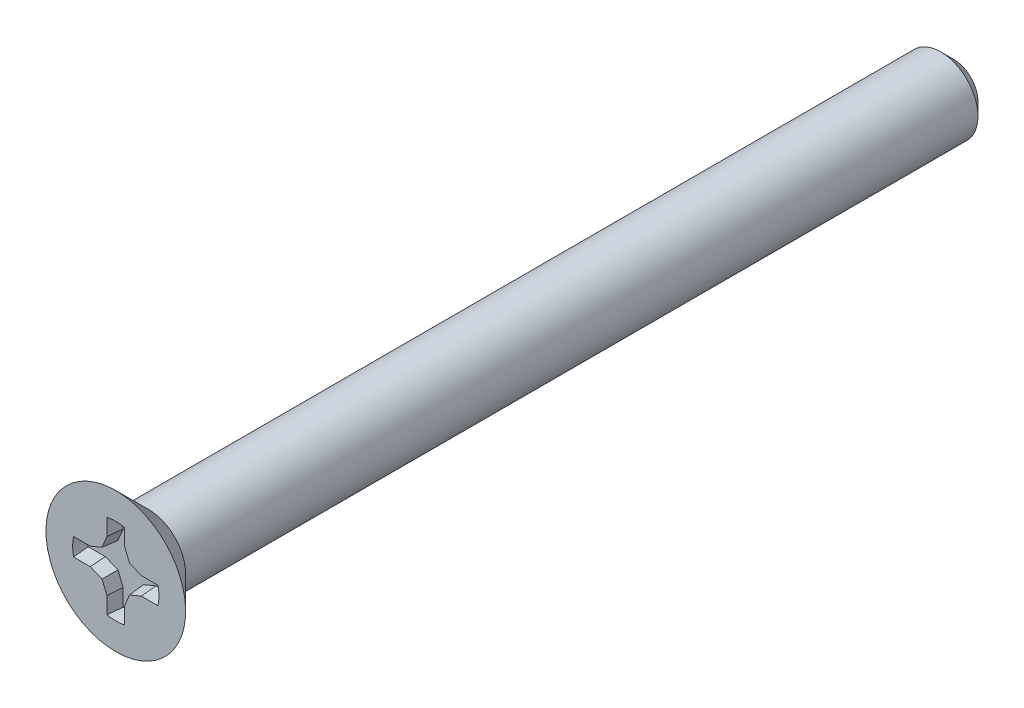
SolidWorks part; units mm, degrees
ref_plane "Front Plane" through (0, 0, 0) normal (0, 0, 1) x (1, 0, 0)
ref_plane "Top Plane" through (0, 0, 0) normal (0, 1, 0) x (1, 0, 0)
ref_plane "Right Plane" through (0, 0, 0) normal (1, 0, 0) x (0, 0, -1)
sketch "Sketch1" plane through (0, 0, 0) normal (1, 0, 0) x (0, 0, -1)
  line L0 (0, 0) -> (-0.96, 0) construction
  line L1 (-0.96, 1.5) -> (-0.96, -1.5) construction
  line L2 (-0.96, 1.5) -> (0, 0.54) construction
  line L3 (-0.96, -1.5) -> (0, -0.54) construction
  line L4 (0, 0.8) -> (0, -0.8) construction
  line L5 (0, 0) -> (17.04, 0) construction
  line L6 (0, 0.8) -> (0.35, 0.8) construction
  line L7 (0, 0.8) -> (-0.26, 0.8) construction
  line L8 (17.04, 0.54) -> (17.04, -0.54) construction
  point P6 (-0.96, 0)
  point P11 (0, 0)
  point P16 (-0.26, 0.8)
  point P17 (15.815, -0.8)
  point P20 (17.04, 0)
  point P21 (-0.48, 0)
  point P22 (15.815, -0.54)
  point P23 (17.04, -0.54)
  point P25 (17.04, 0.54)
  dimension "Head Height" = 0.96
  dimension "Head Diameter" = 3
  dimension "Countersink Angle" = 90
  dimension "Thread OD" = 1.6
  dimension "Length" = 18
  dimension "Thread Pitch" = 0.35
  dimension "D1" = 1.225
sketch "Sketch2" plane through (0, 0, 0) normal (0, 0, 1) x (1, 0, 0)
  line L0 (0.1905, 0.9271) -> (-0.1905, 0.9271) construction
  circle A0 centre (0, 0) radius 0.9271 construction
  point P3 (0, 0.9271)
  point P7 (0, 0.9271)
  dimension "Drive Dia" = 1.8542
  dimension "Drive Width" = 0.381
sketch "Sketch3" plane through (0, 0, 0) normal (1, 0, 0) x (0, 0, -1)
  line L0 (-0.96, 0) -> (-0.96, 1.5)
  line L1 (-0.96, 1.5) -> (-0.26, 0.8)
  line L2 (-0.96, 1.5) -> (0, 0.54) construction
  line L3 (0, 0.8) -> (0.35, 0.8) construction
  line L4 (-0.96, 0) -> (-0.26, 0)
  line L5 (0, 0) -> (-0.96, 0) construction
  line L6 (-0.26, 0) -> (-0.26, 0.8)
revolve "Revolve1" add sketch "Sketch3" angle 360 about L4
sketch "Sketch5" plane through (0, 0, 0) normal (1, 0, 0) x (0, 0, -1)
  line L0 (17.04, 0) -> (-0.26, 0)
  line L1 (0, 0) -> (17.04, 0) construction
  line L2 (-0.26, 0) -> (-0.26, 0.8)
  line L3 (-0.26, 0.8) -> (16.7635, 0.8)
  line L4 (16.7635, 0.8) -> (17.04, 0.5235)
  line L5 (17.04, 0.5235) -> (17.04, 0)
  line L6 (16.7635, 0.8) -> (17.04, 0.8) construction
  line L7 (17.04, 0.8) -> (17.04, 0.5235) construction
  line L8 (0, 0.8) -> (0.35, 0.8) construction
  line L9 (-0.26, -0.8) -> (-0.26, 0.8) construction
  dimension "D1" = 0.2765
revolve "Revolve2" add sketch "Sketch5" angle 360 about L0
sketch "Sketch4" plane through (0, 0, 0.96) normal (0, 0, 1) x (1, 0, 0)
  line L0 (0, 0) -> (0, 0.9271)
  line L1 (0, 0) -> (0.9271, 0)
  line L2 (0, 0) -> (0.5489, 0.5489) construction
  line L3 (0.1905, 0.9073) -> (0.1905, 0.5489)
  line L4 (0.1905, 0.5489) -> (0.1905, 0.1905) construction
  line L5 (0.5489, 0.1905) -> (0.1905, 0.1905) construction
  line L6 (0.9073, 0.1905) -> (0.5489, 0.1905)
  line L7 (0.1905, 0.5489) -> (0.2955, 0.2955)
  line L8 (0.2955, 0.2955) -> (0.5489, 0.1905)
  line L9 (0, 0.9271) -> (0, 1.5) construction
  line L10 (0, 1.5) -> (0, -1.5) construction
  circle A0 centre (0, 0) radius 0.9271 construction
  arc A1 (0, 0.9271) -> (0.1905, 0.9073) centre (0, 0) cw
  arc A2 (0.9271, 0) -> (0.9073, 0.1905) centre (0, 0) ccw
  arc A3 (0.5489, 0.1905) -> (0.1905, 0.5489) centre (0.5489, 0.5489) cw construction
  circle A4 centre (0, 0) radius 1.5 construction
  point P8 (0.2955, 0.2955)
  point P22 (0, -0.9271)
  point P23 (0, 0.9271)
  dimension "D1" = 0.5729
extrude "Cut-Extrude1" cut sketch "Sketch4" against normal blind 0.32 contours L1 A2 L6 L8 L7 L3 A1 L0 region at (0.0131, 0.4635, 0.96)
pattern_circular "CirPattern1" count 4 over 360 about axis through (0, 0, 0) along (0, 0, -1) of "Cut-Extrude1"
draft "Draft2" type of draft neutral plane draft angle 5 faces to draft 16 face at (-0.7281, 0.1905, 0.8) face at (-0.4222, 0.243, 0.8) face at (-0.243, 0.4222, 0.8) face at (-0.1905, 0.7281, 0.8) face at (0.1905, 0.7281, 0.8) face at (0.243, 0.4222, 0.8) face at (0.4222, 0.243, 0.8) face at (0.7281, 0.1905, 0.8) face at (0.7281, -0.1905, 0.8) face at (0.4222, -0.243, 0.8) face at (0.243, -0.4222, 0.8) face at (0.1905, -0.7281, 0.8) face at (-0.1905, -0.7281, 0.8) face at (-0.243, -0.4222, 0.8) face at (-0.4222, -0.243, 0.8) face at (-0.7281, -0.1905, 0.8) neutral plane through (0, 0, 0.96) neutral plane normal (0, 0, 1) parameters "D1"=5
ref_plane "Plane1" through (0, 0, 0.26) normal (0, 0, -1) x (-1, 0, 0)
split "Split1" trim tools "Plane1" bodies to split 107 105 resulting bodies 108 109
sketch "Sketch6" plane through (0, 0, -17.04) normal (0, 0, 1) x (1, 0, 0)
  circle A1 centre (0, 0) radius 0.8
  circle A2 centre (0, 0) radius 0.8
  dimension "D1" = 0
curve "Helix/Spiral1" pitch 0.35 height 18 turns 51.4286
sketch "Sketch7" plane through (0, 0, 0) normal (1, 0, 0) x (0, 0, -1)
  line L0 (17.0181, 0.8379) -> (17.3681, 0.8379) construction
  line L1 (17.0181, 0.8379) -> (17.1931, 0.5348) construction
  line L2 (17.1931, 0.5348) -> (17.3681, 0.8379) construction
  line L3 (17.1713, 0.5727) -> (17.215, 0.5727) construction
  line L4 (17.04, 0.8) -> (17.3463, 0.8) construction
  line L5 (17.1931, 0.8) -> (17.1931, 0.8379) construction
  line L6 (17.1931, 0.5727) -> (17.1931, 0.5348) construction
  line L7 (17.1931, 0.8189) -> (17.0291, 0.8189) construction
  line L10 (17.215, 0.5727) -> (17.1713, 0.5727)
  line L11 (17.0291, 0.8189) -> (17.1713, 0.5727)
  line L12 (17.0291, 0.8189) -> (17.3572, 0.8189)
  line L13 (17.3572, 0.8189) -> (17.215, 0.5727)
  dimension "D1" = 0.35
  dimension "D2" = 0.0437
sweep "Cut-Sweep1" [suppressed] cut profiles "Sketch7" path "Helix/Spiral1"
combine bodies "Combine1" operation type add bodies to combine 109 108
ref_plane "Plane2" through (0, 0, 0.26) normal (0, 0, 1) x (1, 0, 0)
sketch "Sketch8" plane through (0, 0, 0.26) normal (0, 0, 1) x (1, 0, 0)
  circle A0 centre (0, 0) radius 0.8
extrude "Boss-Extrude1" add sketch "Sketch8" against normal up to vertex (0.26 mm away) draft 45 up to point (0, 0.54, 0)
equation "\"D1@Sketch5\" = \"Thread Pitch@Sketch1\" * .79"
equation "\"D4@Helix/Spiral1\" = \"Thread Pitch@Sketch1\""
equation "\"D3@Helix/Spiral1\"=\"Length@Sketch1\""
equation "\"D1@Sketch7\" = \"Thread Pitch@Sketch1\""
equation "\"D2@Sketch7\" = \"Thread Pitch@Sketch1\" / 8"
equation "\"D1@Sketch1\"=\"Thread Pitch@Sketch1\"*3.5"
equation "\"D1@Cut-Extrude1\"=\"Head Height@Sketch1\"/3"
